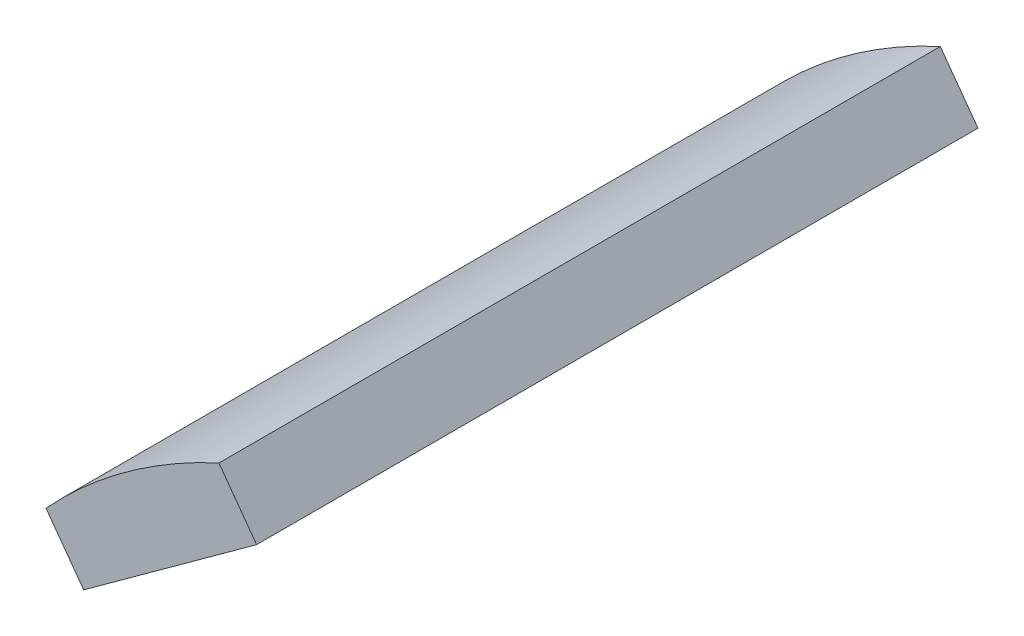
SolidWorks part; units mm, degrees
ref_plane "Ön Düzlem" through (0, 0, 0) normal (0, 0, 1) x (1, 0, 0)
ref_plane "Üst Düzlem" through (0, 0, 0) normal (0, 1, 0) x (1, 0, 0)
ref_plane "Sağ Düzlem" through (0, 0, 0) normal (1, 0, 0) x (0, 0, -1)
sketch "Sketch1" plane through (0, 0, 0) normal (0, 0, 1) x (1, 0, 0)
  line L0 (0, 0) -> (0, 81.5)
  line L1 (10, 81.5) -> (-10, 81.5)
  line L2 (-10, 81.5) -> (-10, 87.5)
  line L3 (10, 81.5) -> (10, 87.5)
  line L4 (15.6743, 80.6013) -> (17.5284, 86.3076)
  line L5 (34.6955, 74.4209) -> (36.5496, 80.1273)
  line L6 (34.6955, 74.4209) -> (15.6743, 80.6013)
  line L7 (39.8143, 71.8127) -> (43.341, 76.6668)
  line L8 (55.9947, 60.057) -> (59.5214, 64.9111)
  line L9 (55.9947, 60.057) -> (39.8143, 71.8127)
  line L10 (60.057, 55.9947) -> (64.9111, 59.5214)
  line L11 (71.8127, 39.8143) -> (76.6668, 43.341)
  line L12 (71.8127, 39.8143) -> (60.057, 55.9947)
  line L13 (74.4209, 34.6955) -> (80.1273, 36.5496)
  line L14 (80.6013, 15.6743) -> (86.3076, 17.5284)
  line L15 (80.6013, 15.6743) -> (74.4209, 34.6955)
  line L16 (81.5, 10) -> (87.5, 10)
  line L17 (81.5, -10) -> (87.5, -10)
  line L18 (81.5, -10) -> (81.5, 10)
  line L19 (80.6013, -15.6743) -> (86.3076, -17.5284)
  line L20 (74.4209, -34.6955) -> (80.1273, -36.5496)
  line L21 (74.4209, -34.6955) -> (80.6013, -15.6743)
  line L22 (71.8127, -39.8143) -> (76.6668, -43.341)
  line L23 (60.057, -55.9947) -> (64.9111, -59.5214)
  line L24 (60.057, -55.9947) -> (71.8127, -39.8143)
  line L25 (55.9947, -60.057) -> (59.5214, -64.9111)
  line L26 (39.8143, -71.8127) -> (43.341, -76.6668)
  line L27 (39.8143, -71.8127) -> (55.9947, -60.057)
  line L28 (34.6955, -74.4209) -> (36.5496, -80.1273)
  line L29 (15.6743, -80.6013) -> (17.5284, -86.3076)
  line L30 (15.6743, -80.6013) -> (34.6955, -74.4209)
  line L31 (10, -81.5) -> (10, -87.5)
  line L32 (-10, -81.5) -> (-10, -87.5)
  line L33 (-10, -81.5) -> (10, -81.5)
  line L34 (-15.6743, -80.6013) -> (-17.5284, -86.3076)
  line L35 (-34.6955, -74.4209) -> (-36.5496, -80.1273)
  line L36 (-34.6955, -74.4209) -> (-15.6743, -80.6013)
  line L37 (-39.8143, -71.8127) -> (-43.341, -76.6668)
  line L38 (-55.9947, -60.057) -> (-59.5214, -64.9111)
  line L39 (-55.9947, -60.057) -> (-39.8143, -71.8127)
  line L40 (-60.057, -55.9947) -> (-64.9111, -59.5214)
  line L41 (-71.8127, -39.8143) -> (-76.6668, -43.341)
  line L42 (-71.8127, -39.8143) -> (-60.057, -55.9947)
  line L43 (-74.4209, -34.6955) -> (-80.1273, -36.5496)
  line L44 (-80.6013, -15.6743) -> (-86.3076, -17.5284)
  line L45 (-80.6013, -15.6743) -> (-74.4209, -34.6955)
  line L46 (-81.5, -10) -> (-87.5, -10)
  line L47 (-81.5, 10) -> (-87.5, 10)
  line L48 (-81.5, 10) -> (-81.5, -10)
  line L49 (-80.6013, 15.6743) -> (-86.3076, 17.5284)
  line L50 (-74.4209, 34.6955) -> (-80.1273, 36.5496)
  line L51 (-74.4209, 34.6955) -> (-80.6013, 15.6743)
  line L52 (-71.8127, 39.8143) -> (-76.6668, 43.341)
  line L53 (-60.057, 55.9947) -> (-64.9111, 59.5214)
  line L54 (-60.057, 55.9947) -> (-71.8127, 39.8143)
  line L55 (-55.9947, 60.057) -> (-59.5214, 64.9111)
  line L56 (-39.8143, 71.8127) -> (-43.341, 76.6668)
  line L57 (-39.8143, 71.8127) -> (-55.9947, 60.057)
  line L58 (-34.6955, 74.4209) -> (-36.5496, 80.1273)
  line L59 (-15.6743, 80.6013) -> (-17.5284, 86.3076)
  line L60 (-15.6743, 80.6013) -> (-34.6955, 74.4209)
  line L61 (34.6955, 74.4209) -> (34.7846, 74.3755)
  line L62 (35.1494, 75.3119) -> (40.2683, 72.7037) construction
  line L63 (39.7252, 71.8581) -> (39.8143, 71.8127)
  line L64 (35.2385, 75.2665) -> (40.1792, 72.7491)
  line L65 (34.7846, 74.3755) -> (35.2385, 75.2665)
  line L66 (55.9947, 60.057) -> (56.0654, 59.9863)
  line L67 (39.7252, 71.8581) -> (40.1792, 72.7491)
  line L68 (34.7846, 74.3755) -> (35.1931, 75.1774) construction
  line L69 (39.7252, 71.8581) -> (40.1338, 72.66) construction
  line L70 (35.1931, 75.1774) -> (40.1338, 72.66) construction
  line L71 (34.6955, 74.4209) -> (35.1494, 75.3119) construction
  line L72 (39.8143, 71.8127) -> (40.2683, 72.7037) construction
  line L73 (56.0654, 59.9863) -> (56.7725, 60.6934)
  line L74 (56.7725, 60.6934) -> (60.6934, 56.7725)
  line L75 (59.9863, 56.0654) -> (60.6934, 56.7725)
  line L76 (59.9863, 56.0654) -> (60.057, 55.9947)
  line L77 (71.8127, 39.8143) -> (71.8581, 39.7252)
  line L78 (71.8581, 39.7252) -> (72.7491, 40.1792)
  line L79 (72.7491, 40.1792) -> (75.2665, 35.2385)
  line L80 (74.3755, 34.7846) -> (75.2665, 35.2385)
  line L81 (74.3755, 34.7846) -> (74.4209, 34.6955)
  line L82 (80.6013, 15.6743) -> (80.6169, 15.5756)
  line L83 (80.6169, 15.5756) -> (81.6046, 15.732)
  line L84 (81.6046, 15.732) -> (82.472, 10.2552)
  line L85 (81.4844, 10.0988) -> (82.472, 10.2552)
  line L86 (81.4844, 10.0988) -> (81.5, 10)
  line L87 (81.5, -10) -> (81.4844, -10.0988)
  line L88 (81.4844, -10.0988) -> (82.472, -10.2552)
  line L89 (82.472, -10.2552) -> (81.6046, -15.732)
  line L90 (80.6169, -15.5756) -> (81.6046, -15.732)
  line L91 (80.6169, -15.5756) -> (80.6013, -15.6743)
  line L92 (74.4209, -34.6955) -> (74.3755, -34.7846)
  line L93 (74.3755, -34.7846) -> (75.2665, -35.2385)
  line L94 (75.2665, -35.2385) -> (72.7491, -40.1792)
  line L95 (71.8581, -39.7252) -> (72.7491, -40.1792)
  line L96 (71.8581, -39.7252) -> (71.8127, -39.8143)
  line L97 (60.057, -55.9947) -> (59.9863, -56.0654)
  line L98 (59.9863, -56.0654) -> (60.6934, -56.7725)
  line L99 (60.6934, -56.7725) -> (56.7725, -60.6934)
  line L100 (56.0654, -59.9863) -> (56.7725, -60.6934)
  line L101 (56.0654, -59.9863) -> (55.9947, -60.057)
  line L102 (39.8143, -71.8127) -> (39.7252, -71.8581)
  line L103 (39.7252, -71.8581) -> (40.1792, -72.7491)
  line L104 (40.1792, -72.7491) -> (35.2385, -75.2665)
  line L105 (34.7846, -74.3755) -> (35.2385, -75.2665)
  line L106 (34.7846, -74.3755) -> (34.6955, -74.4209)
  line L107 (15.6743, -80.6013) -> (15.5756, -80.6169)
  line L108 (15.5756, -80.6169) -> (15.732, -81.6046)
  line L109 (15.732, -81.6046) -> (10.2552, -82.472)
  line L110 (10.0988, -81.4844) -> (10.2552, -82.472)
  line L111 (10.0988, -81.4844) -> (10, -81.5)
  line L112 (-10, -81.5) -> (-10.0988, -81.4844)
  line L113 (-10.0988, -81.4844) -> (-10.2552, -82.472)
  line L114 (-10.2552, -82.472) -> (-15.732, -81.6046)
  line L115 (-15.5756, -80.6169) -> (-15.732, -81.6046)
  line L116 (-15.5756, -80.6169) -> (-15.6743, -80.6013)
  line L117 (-34.6955, -74.4209) -> (-34.7846, -74.3755)
  line L118 (-34.7846, -74.3755) -> (-35.2385, -75.2665)
  line L119 (-35.2385, -75.2665) -> (-40.1792, -72.7491)
  line L120 (-39.7252, -71.8581) -> (-40.1792, -72.7491)
  line L121 (-39.7252, -71.8581) -> (-39.8143, -71.8127)
  line L122 (-55.9947, -60.057) -> (-56.0654, -59.9863)
  line L123 (-56.0654, -59.9863) -> (-56.7725, -60.6934)
  line L124 (-56.7725, -60.6934) -> (-60.6934, -56.7725)
  line L125 (-59.9863, -56.0654) -> (-60.6934, -56.7725)
  line L126 (-59.9863, -56.0654) -> (-60.057, -55.9947)
  line L127 (-71.8127, -39.8143) -> (-71.8581, -39.7252)
  line L128 (-71.8581, -39.7252) -> (-72.7491, -40.1792)
  line L129 (-72.7491, -40.1792) -> (-75.2665, -35.2385)
  line L130 (-74.3755, -34.7846) -> (-75.2665, -35.2385)
  line L131 (-74.3755, -34.7846) -> (-74.4209, -34.6955)
  line L132 (-80.6013, -15.6743) -> (-80.6169, -15.5756)
  line L133 (-80.6169, -15.5756) -> (-81.6046, -15.732)
  line L134 (-81.6046, -15.732) -> (-82.472, -10.2552)
  line L135 (-81.4844, -10.0988) -> (-82.472, -10.2552)
  line L136 (-81.4844, -10.0988) -> (-81.5, -10)
  line L137 (-81.5, 10) -> (-81.4844, 10.0988)
  line L138 (-81.4844, 10.0988) -> (-82.472, 10.2552)
  line L139 (-82.472, 10.2552) -> (-81.6046, 15.732)
  line L140 (-80.6169, 15.5756) -> (-81.6046, 15.732)
  line L141 (-80.6169, 15.5756) -> (-80.6013, 15.6743)
  line L142 (-74.4209, 34.6955) -> (-74.3755, 34.7846)
  line L143 (-74.3755, 34.7846) -> (-75.2665, 35.2385)
  line L144 (-75.2665, 35.2385) -> (-72.7491, 40.1792)
  line L145 (-71.8581, 39.7252) -> (-72.7491, 40.1792)
  line L146 (-71.8581, 39.7252) -> (-71.8127, 39.8143)
  line L147 (-60.057, 55.9947) -> (-59.9863, 56.0654)
  line L148 (-59.9863, 56.0654) -> (-60.6934, 56.7725)
  line L149 (-60.6934, 56.7725) -> (-56.7725, 60.6934)
  line L150 (-56.0654, 59.9863) -> (-56.7725, 60.6934)
  line L151 (-56.0654, 59.9863) -> (-55.9947, 60.057)
  line L152 (-39.8143, 71.8127) -> (-39.7252, 71.8581)
  line L153 (-39.7252, 71.8581) -> (-40.1792, 72.7491)
  line L154 (-40.1792, 72.7491) -> (-35.2385, 75.2665)
  line L155 (-34.7846, 74.3755) -> (-35.2385, 75.2665)
  line L156 (-34.7846, 74.3755) -> (-34.6955, 74.4209)
  line L157 (-15.6743, 80.6013) -> (-15.5756, 80.6169)
  line L158 (-15.5756, 80.6169) -> (-15.732, 81.6046)
  line L159 (-15.732, 81.6046) -> (-10.2552, 82.472)
  line L160 (-10.0988, 81.4844) -> (-10.2552, 82.472)
  line L161 (-10.0988, 81.4844) -> (-10, 81.5)
  line L162 (10, 81.5) -> (10.0988, 81.4844)
  line L163 (10.0988, 81.4844) -> (10.2552, 82.472)
  line L164 (10.2552, 82.472) -> (15.732, 81.6046)
  line L165 (15.5756, 80.6169) -> (15.732, 81.6046)
  line L166 (15.5756, 80.6169) -> (15.6743, 80.6013)
  circle A0 centre (0, 0) radius 60
  arc A2 (10, 87.5) -> (-10, 87.5) centre (0, 38) ccw
  arc A3 (36.5496, 80.1273) -> (17.5284, 86.3076) centre (11.7426, 36.1401) ccw
  arc A4 (59.5214, 64.9111) -> (43.341, 76.6668) centre (22.3358, 30.7426) ccw
  arc A5 (76.6668, 43.341) -> (64.9111, 59.5214) centre (30.7426, 22.3358) ccw
  arc A6 (86.3076, 17.5284) -> (80.1273, 36.5496) centre (36.1401, 11.7426) ccw
  arc A7 (87.5, -10) -> (87.5, 10) centre (38, 0) ccw
  arc A8 (80.1273, -36.5496) -> (86.3076, -17.5284) centre (36.1401, -11.7426) ccw
  arc A9 (64.9111, -59.5214) -> (76.6668, -43.341) centre (30.7426, -22.3358) ccw
  arc A10 (43.341, -76.6668) -> (59.5214, -64.9111) centre (22.3358, -30.7426) ccw
  arc A11 (17.5284, -86.3076) -> (36.5496, -80.1273) centre (11.7426, -36.1401) ccw
  arc A12 (-10, -87.5) -> (10, -87.5) centre (0, -38) ccw
  arc A13 (-36.5496, -80.1273) -> (-17.5284, -86.3076) centre (-11.7426, -36.1401) ccw
  arc A14 (-59.5214, -64.9111) -> (-43.341, -76.6668) centre (-22.3358, -30.7426) ccw
  arc A15 (-76.6668, -43.341) -> (-64.9111, -59.5214) centre (-30.7426, -22.3358) ccw
  arc A16 (-86.3076, -17.5284) -> (-80.1273, -36.5496) centre (-36.1401, -11.7426) ccw
  arc A17 (-87.5, 10) -> (-87.5, -10) centre (-38, 0) ccw
  arc A18 (-80.1273, 36.5496) -> (-86.3076, 17.5284) centre (-36.1401, 11.7426) ccw
  arc A19 (-64.9111, 59.5214) -> (-76.6668, 43.341) centre (-30.7426, 22.3358) ccw
  arc A20 (-43.341, 76.6668) -> (-59.5214, 64.9111) centre (-22.3358, 30.7426) ccw
  arc A21 (-17.5284, 86.3076) -> (-36.5496, 80.1273) centre (-11.7426, 36.1401) ccw
  point P7 (0, 81.5)
  point P107 (0, 0)
  point P231 (0, 0)
  dimension "D1" = 81.5
  dimension "D3" = 50.5
  dimension "D2" = 20
  dimension "D4" = 6
  dimension "D5" = 6
  dimension "D7" = 20
  dimension "D6" = 20
extrude "Boss-Extrude2" add sketch "Sketch1" along normal blind 67.5 contours L56 A20 L55 L57 region at (-49.8681, 68.6375, 0)
